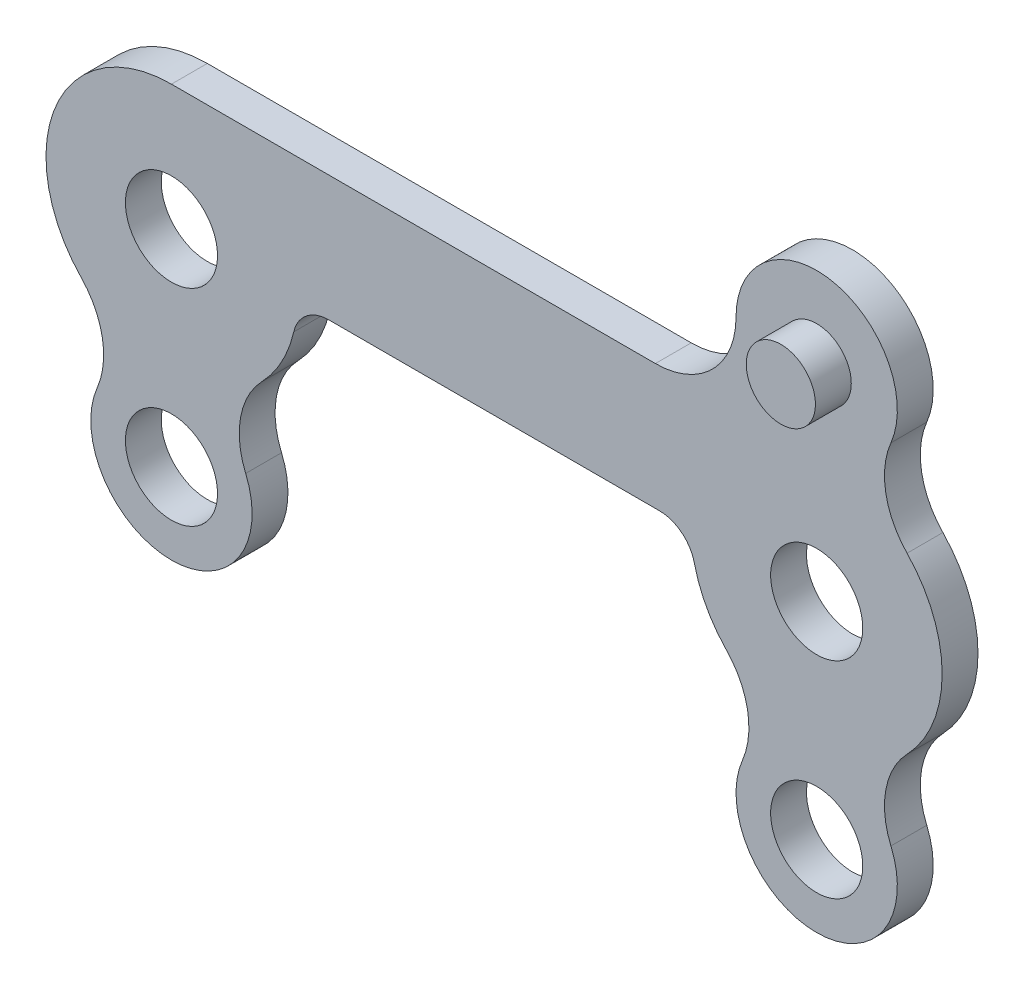
SolidWorks part; units mm, degrees
material "ABS"
ref_plane "Front Plane" through (0, 0, 0) normal (0, 0, 1) x (1, 0, 0)
ref_plane "Top Plane" through (0, 0, 0) normal (0, 1, 0) x (1, 0, 0)
ref_plane "Right Plane" through (0, 0, 0) normal (1, 0, 0) x (0, 0, -1)
sketch "Sketch1" plane through (0, 0, 0) normal (0, 0, 1) x (1, 0, 0)
  line L0 (5.5562, 0) -> (23.0188, 0)
  line L1 (0, 5.5562) -> (28.575, 5.5562)
  line L5 (0, 5.5562) -> (28.575, 5.5562) construction
  circle A0 centre (0, 0) radius 5.5562 construction
  circle A1 centre (28.575, 0) radius 5.5562 construction
  arc A2 (0, 5.5562) -> (0, -5.5562) centre (0, 0) ccw
  arc A3 (28.575, -5.5562) -> (28.575, 5.5562) centre (28.575, 0) ccw
  circle A4 centre (0, 0) radius 1.7859
  circle A5 centre (28.575, 0) radius 1.7859
  arc A6 (0, -5.5562) -> (5.5562, 0) centre (0, 0) ccw
  arc A7 (23.0188, 0) -> (28.575, -5.5562) centre (28.575, 0) ccw
  circle A10 centre (0, -9.1281) radius 3.5719
  circle A12 centre (28.575, -9.1281) radius 1.7859
  circle A15 centre (0, -9.1281) radius 1.7859
  circle A17 centre (28.575, -9.1281) radius 3.5719
  circle A27 centre (-6.5741, -6.3327) radius 3.5719
  circle A28 centre (6.5741, -6.3327) radius 3.5719
  circle A29 centre (22.0009, -6.3327) radius 3.5719
  circle A30 centre (35.1491, -6.3327) radius 3.5719
  circle A31 centre (28.575, 9.1281) radius 1.7859
  circle A32 centre (28.575, 9.1281) radius 3.5719
  circle A33 centre (21.4313, 9.1281) radius 3.5719
  circle A34 centre (35.1491, 6.3327) radius 3.5719
  dimension "D1" = 28.575
  dimension "D2" = 11.1125
  dimension "D3" = 3.5719
  dimension "D6" = 7.1437
  dimension "D7" = 3.5719
sketch "Sketch2" plane through (0, 0, 0) normal (0, 0, 1) x (1, 0, 0)
  line L0 (5.5562, 0) -> (23.0188, 0)
  line L2 (0, 5.5562) -> (28.575, 5.5562)
  circle A0 centre (0, 0) radius 5.5562
  circle A1 centre (28.575, 0) radius 5.5563
  circle A2 centre (28.575, -9.1281) radius 3.5719
  circle A3 centre (0, -9.1281) radius 3.5719
  circle A4 centre (6.5741, -6.3327) radius 3.5719
  circle A5 centre (-6.5741, -6.3327) radius 3.5719
  circle A6 centre (22.0009, -6.3327) radius 3.5719
  circle A7 centre (35.1491, -6.3327) radius 3.5719
  circle A8 centre (28.575, 9.1281) radius 3.5719
  arc A9 (0, -5.5562) -> (5.5562, 0) centre (0, 0) ccw construction
  arc A10 (23.0188, 0) -> (28.575, -5.5562) centre (28.575, 0) ccw construction
  circle A11 centre (28.575, -9.1281) radius 3.5719 construction
  circle A12 centre (0, -9.1281) radius 3.5719 construction
  circle A13 centre (22.0009, -6.3327) radius 3.5719 construction
  circle A15 centre (28.575, 9.1281) radius 3.5719 construction
  circle A16 centre (35.1491, 6.3327) radius 3.5719
  circle A18 centre (35.1491, 6.3327) radius 3.5719 construction
  circle A19 centre (0, 0) radius 2.0399
  circle A20 centre (28.575, 0) radius 2.0399
  circle A21 centre (0, -9.1281) radius 2.0399
  circle A22 centre (28.575, -9.1281) radius 2.0399
  circle A28 centre (28.575, 9.1281) radius 1.5319
  circle A30 centre (21.4313, 9.1281) radius 3.5719
  circle A31 centre (21.4313, 9.1281) radius 3.5719 construction
  dimension "D1" = 4.0799
  dimension "D2" = 4.0799
  dimension "D3" = 3.0639
extrude "Boss-Extrude1" add sketch "Sketch2" along normal blind 1.5875 contours A0 A19 | A5 A3 A0 | A4 A0 A3 | A3 A21 | A2 A22 | A6 A2 A1 | A7 A1 A2 | A1 A20 | A1 L2 A0 L0 | A30 L2 A8 | A16 A8 A1 | A8 A28 region at (14.2875, 2.9628, 0) region at (5.0072, -2.0194, 0) region at (24.7573, 3.8177, 0) region at (2.4105, -5.669, 0) region at (30.9855, 5.669, 0) region at (25.0031, 6.3541, 0) region at (26.1207, 6.6739, 0) region at (26.1645, -5.669, 0) region at (-2.4105, -5.669, 0) region at (1.9148, -6.2332, 0) region at (30.9855, -5.669, 0) region at (30.4898, -6.2332, 0)
extrude "Boss-Extrude3" add sketch "Sketch2<4>" along normal blind 3.175 contours A28 region at (28.575, 9.1281, 0)
sketch "Sketch2<4>" plane through (0, 0, 0) normal (0, 0, 1) x (1, 0, 0) same geometry as "Sketch2"
fillet "Fillet1" radius 1.5875 2 edges at (23.0188, 0, 0.7937) (5.5562, 0, 0.7937)
